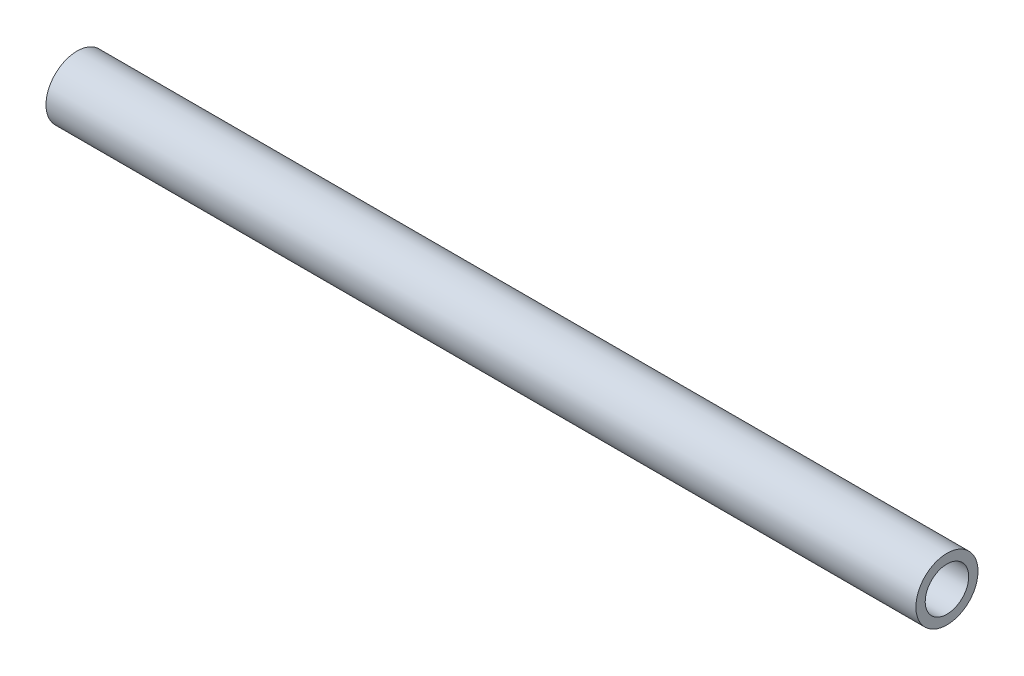
SolidWorks part; units mm, degrees
ref_plane "Front Plane" through (0, 0, 0) normal (0, 0, 1) x (1, 0, 0)
ref_plane "Top Plane" through (0, 0, 0) normal (0, 1, 0) x (1, 0, 0)
ref_plane "Right Plane" through (0, 0, 0) normal (1, 0, 0) x (0, 0, -1)
sketch "Sketch1" plane through (0, 0, 0) normal (0, 0, 1) x (1, 0, 0)
  line L0 (-70, 0) -> (70, 0)
  point P4 (0, 0)
  dimension "D1" = 140
sweep "Sweep-Thin1" add path "Sketch1" circular profile diameter 10 parameters "D1"=1.5, "D3"=10
